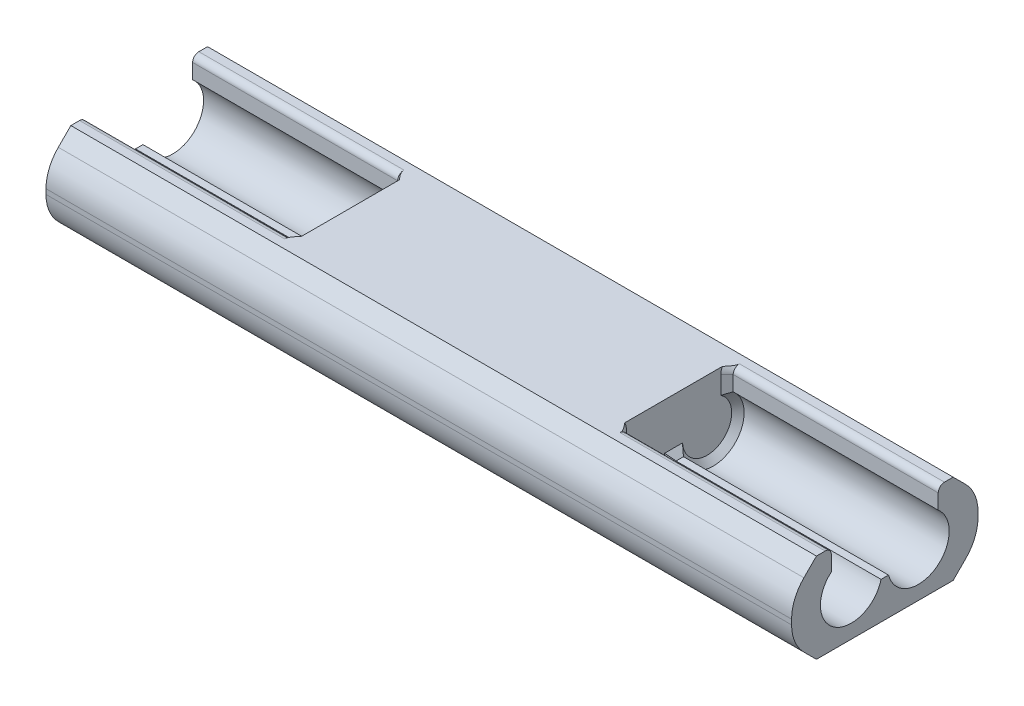
SolidWorks part; units mm, degrees
ref_plane "Front Plane" through (0, 0, 0) normal (0, 0, 1) x (1, 0, 0)
ref_plane "Top Plane" through (0, 0, 0) normal (0, 1, 0) x (1, 0, 0)
ref_plane "Right Plane" through (0, 0, 0) normal (1, 0, 0) x (0, 0, -1)
other "Configuration Table"
sketch "Sketch1" plane through (0, 0, 0) normal (1, 0, 0) x (0, 0, -1)
  line L0 (-1.7145, 0) -> (1.7145, 0) construction
  line L1 (-1.7145, 2.286) -> (-1.7145, 0) construction
  line L2 (3.4925, -2.286) -> (-3.4925, -2.286)
  line L3 (4.7625, -0.127) -> (4.7625, 0.127)
  line L4 (3.4925, 2.286) -> (-3.4925, 2.286)
  line L5 (-4.7625, -0.127) -> (-4.7625, 0.127)
  line L6 (4.7625, -2.286) -> (-4.7625, 2.286) construction
  line L7 (4.7625, 2.286) -> (-4.7625, -2.286) construction
  line L8 (-1.7145, 0) -> (-4.7625, 0) construction
  line L9 (3.4925, -2.286) -> (4.1339, -1.6446)
  line L10 (4.1339, 1.6446) -> (3.4925, 2.286)
  line L11 (-4.1339, 1.6446) -> (-3.4925, 2.286)
  line L12 (-4.1339, -1.6446) -> (-3.4925, -2.286)
  line L13 (0, -2.286) -> (0, 2.286) construction
  line L14 (-3.4925, 2.286) -> (-4.7625, 2.286) construction
  line L15 (-4.7625, 1.016) -> (-4.7625, 2.286) construction
  line L16 (-4.7625, -2.286) -> (-4.7625, -1.016) construction
  line L17 (-3.4925, -2.286) -> (-4.7625, -2.286) construction
  line L18 (4.7625, -2.286) -> (3.4925, -2.286) construction
  line L19 (4.7625, -2.286) -> (4.7625, -1.016) construction
  line L20 (4.7625, 1.016) -> (4.7625, 2.286) construction
  line L21 (4.7625, 2.286) -> (3.4925, 2.286) construction
  circle A0 centre (-1.7145, 0) radius 1.5
  circle A1 centre (1.7145, 0) radius 1.5
  arc A2 (-4.1339, 1.6446) -> (-4.7625, 0.127) centre (-2.6163, 0.127) ccw
  arc A3 (-4.1339, -1.6446) -> (-4.7625, -0.127) centre (-2.6163, -0.127) cw
  arc A4 (4.1339, -1.6446) -> (4.7625, -0.127) centre (2.6163, -0.127) ccw
  arc A5 (4.7625, 0.127) -> (4.1339, 1.6446) centre (2.6163, 0.127) ccw
  point P5 (0, 0)
  dimension "D2" = 3
  dimension "D1" = 3.429
  dimension "D3" = 4.572
  dimension "D4" = 9.525
  dimension "D5" = 45
  dimension "D6" = 1.27
  dimension "D7" = 0.254
extrude "Boss-Extrude1" add sketch "Sketch1" along normal blind 19.05 contours L2 L12 A3 L5 A2 L11 L4 L10 A5 L3 A4 L9
sketch "Sketch2" plane through (19.05, 0, 0) normal (1, 0, 0) x (0, 0, -1)
  line L0 (-2.7305, 1.2035) -> (-2.7305, 2.286)
  line L1 (3.4925, 2.286) -> (-3.4925, 2.286) construction
  line L2 (-2.7305, 2.286) -> (2.7305, 2.286)
  line L3 (2.7305, 2.286) -> (2.7305, 1.2035)
  line L4 (2.7305, 1.2035) -> (0.1905, -0.3976)
  line L5 (0.1905, -0.3976) -> (-0.1905, -0.3976)
  line L6 (-0.1905, -0.3976) -> (-2.7305, 1.2035)
  circle A0 centre (1.7145, 0) radius 1.5 construction
  circle A1 centre (-1.7145, 0) radius 1.5 construction
  circle A2 centre (1.7145, 0) radius 1.5 construction
  circle A3 centre (-1.7145, 0) radius 1.5 construction
  circle A4 centre (-1.7145, 0) radius 1.575
  circle A5 centre (1.7145, 0) radius 1.575
  line M16 (3.4925, 2.286) -> (-3.4925, 2.286)
  dimension "D1" = 3.15
  dimension "D2" = 0.381
  dimension "D3" = 1.016
extrude "Cut-Extrude1" cut sketch "Sketch2" against normal blind 10.795 contours L6 A4 | A5 L3 L0 A4 L5 M16 | L6 A4 | L4 A5 | L4 A5 region at (19.05, 0.7887, 1.2173) region at (19.05, 1.6466, 0) region at (19.05, -0.3551, 1.9383) region at (19.05, 0.7887, -1.2173) region at (19.05, -0.3551, -1.9383)
fillet "Fillet1" radius 0.3175 2 edges at (13.6525, 2.286, -2.7305) (13.6525, 2.286, 2.7305)
chamfer "Chamfer1" distance 0.3175 angle 45 7 edges at (8.255, 2.193, -2.8235) (8.255, 1.586, -2.7305) (8.255, -1.3324, -2.5543) (8.255, -0.3976, 0) (8.255, 2.193, 2.8235) (8.255, 1.586, 2.7305) (8.255, -1.3324, 2.5543)
mirror "Mirror1" about plane through (0, 0, 0) normal (1, 0, 0) of bodies 102
equation "\"Width\" = 1.5in"
equation "\"D4@Sketch1\"=\"ProfileWidth\""
equation "\"Height\"= 0.18in"
equation "\"D3@Sketch1\"=\"ProfileHeight\""
equation "\"DowelSpacing\"= 0.135in"
equation "\"D1@Sketch1\"=\"DowelSpacing\""
equation "\"D1@Boss-Extrude1\"=\"Width\"/2"
equation "\"ProfileWidth\"= .375in"
equation "\"ProfileHeight\"= .18in"
equation "\"DowelClearance\" = 3mm + .15mm"
equation "\"D1@Sketch2\"=\"DowelClearance\""
equation "\"D1@Cut-Extrude1\"=\"DowelDepth\""
equation "\"InnerWidth\" = .65in"
equation "\"DowelDepth\"= ( \"Width\" - \"InnerWidth\" ) / 2"
